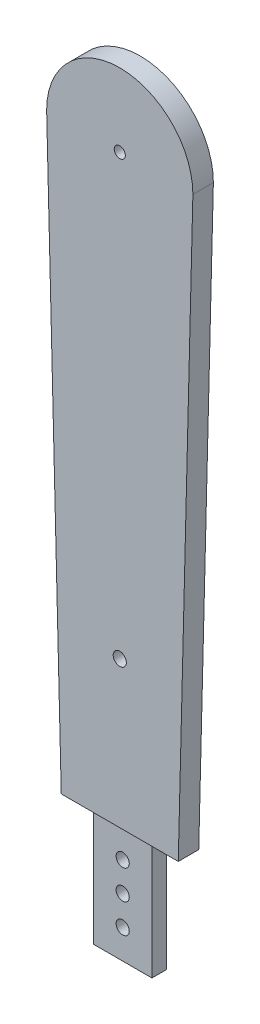
SolidWorks part; units mm, degrees
other "Markup1"
sketch "Sketch21" plane through (-25, -390, 7) normal (-0.035, -0.0156, 0.9993) x (0.9974, 0.0629, 0.0359)
other "Markup2"
sketch "Sketch22" plane through (-25, -390, 7) normal (-0.218, -0.9748, 0.047) x (0.9498, -0.2008, 0.2398)
ref_plane "Front Plane" through (0, 0, 0) normal (0, 0, 1) x (1, 0, 0)
ref_plane "Top Plane" through (0, 0, 0) normal (0, 1, 0) x (1, 0, 0)
ref_plane "Right Plane" through (0, 0, 0) normal (1, 0, 0) x (0, 0, -1)
sketch "Sketch7" plane through (0, 0, 0) normal (0, 0, 1) x (1, 0, 0)
  line L0 (-25, 0) -> (-20, -200)
  line L1 (-20, -200) -> (20, -200)
  line L2 (25, 0) -> (20, -200)
  arc A0 (25, 0) -> (-25, 0) centre (0, 0) ccw
  arc A1 (-24.9688, -1.2492) -> (24.9688, -1.2492) centre (0, 0) ccw
  point P9 (0, -200)
  dimension "D2" = 50
  dimension "D1" = 200
  dimension "D3" = 40
extrude "Boss-Extrude3" add sketch "Sketch7" along normal mid plane 7 contours L0 A1 L2 A0 | A1 L0 L1 L2 region at (0, 0, 0) region at (0, -106.7874, 0)
ref_plane "Plane2" through (0, 0, 0) normal (0, 0, 1) x (1, 0, 0)
sketch "Sketch14" plane through (0, -200, 0) normal (0, -1, 0) x (1, 0, 0)
  line L1 (-10, -2.5) -> (10, -2.5)
  line L2 (-10, -2.5) -> (-10, 2.5)
  line L3 (-10, 2.5) -> (10, 2.5)
  line L4 (10, -2.5) -> (10, 2.5)
  line L5 (-10, -2.5) -> (10, 2.5) construction
  line L6 (-10, 2.5) -> (10, -2.5) construction
  point P0 (0, 0)
  dimension "D1" = 20
  dimension "D2" = 5
sketch "Sketch17" plane through (0, 0, 3.5) normal (0, 0, 1) x (1, 0, 0)
  circle A0 centre (0, 0) radius 1.9
  dimension "D1" = 3.8
sketch "Sketch18" plane through (0, 0, 3.5) normal (0, 0, 1) x (1, 0, 0)
  circle A0 centre (0, -150) radius 2.25
  dimension "D1" = 4.5
  dimension "D2" = 150
extrude "Cut-Extrude10" cut sketch "Sketch18" against normal blind 14
extrude "Cut-Extrude13" cut sketch "Sketch17" against normal mid plane 48
extrude "Boss-Extrude4" add sketch "Sketch14" along normal blind 40
sketch "Sketch23" plane through (0, 0, 3.5) normal (0, 0, 1) x (1, 0, 0)
  line L0 (0, -150) -> (0, -240)
  line L1 (10, -240) -> (-10, -240) construction
  line L2 (-20, -200) -> (20, -200) construction
  circle A0 centre (0, -210) radius 2.25
  circle A1 centre (0, -220) radius 2.25
  circle A2 centre (0, -230) radius 2.25
  dimension "D1" = 4.5
  dimension "D3" = 10
  dimension "D2" = 3
extrude "Cut-Extrude15" cut sketch "Sketch23" against normal blind 7 contours L0 A0 | L0 A0 | L0 A1 | L0 A1 | L0 A2 | L0 A2 region at (0.9549, -210, 3.5) region at (0.9549, -230, 3.5) region at (-0.9549, -230, 3.5) region at (0.9549, -220, 3.5) region at (-0.9549, -220, 3.5) region at (-0.9549, -210, 3.5)
